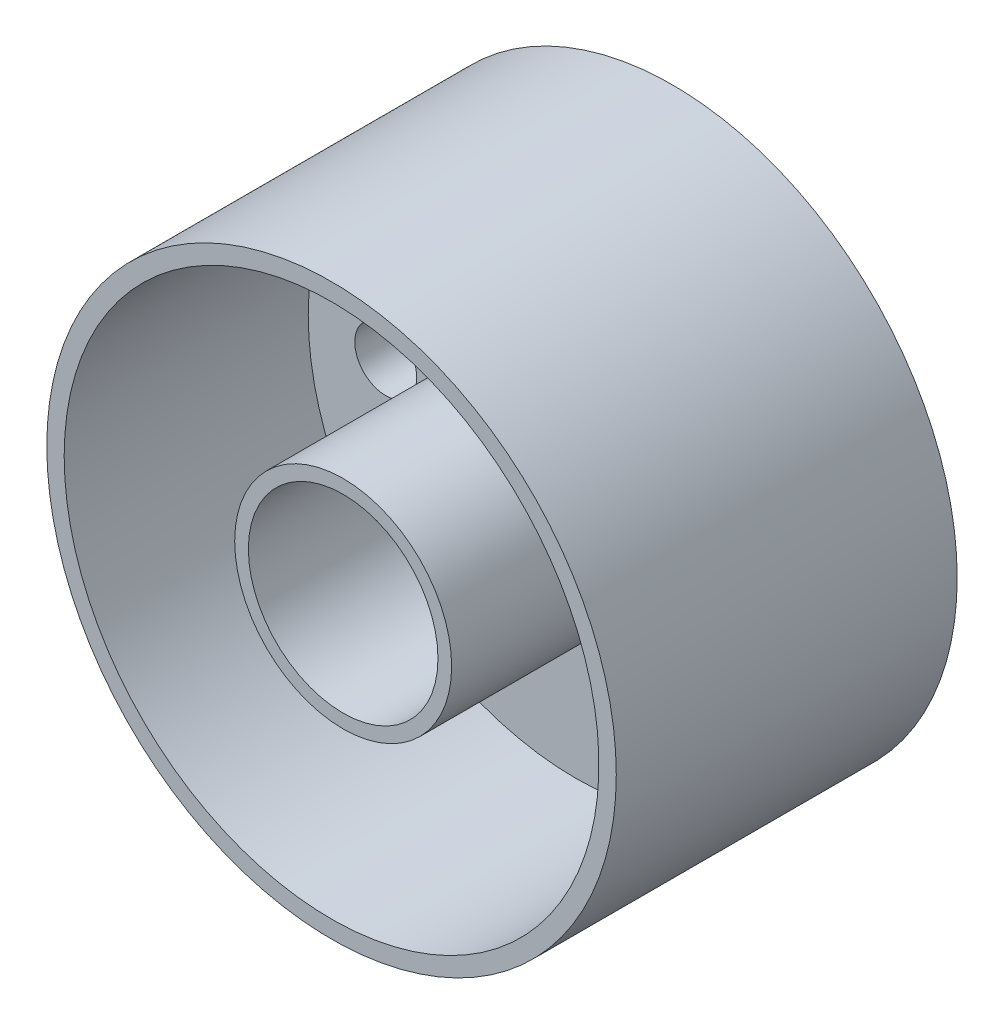
SolidWorks part; units mm, degrees
ref_plane "Front Plane" through (0, 0, 0) normal (0, 0, 1) x (1, 0, 0)
ref_plane "Top Plane" through (0, 0, 0) normal (0, 1, 0) x (1, 0, 0)
ref_plane "Right Plane" through (0, 0, 0) normal (1, 0, 0) x (0, 0, -1)
sketch "Sketch1" plane through (0, 0, 0) normal (0, 0, 1) x (1, 0, 0)
  line L0 (-2.45, 0) -> (-7.35, 0) construction
  circle A0 centre (0, 0) radius 2.45
  circle A1 centre (0, 0) radius 7.35
  circle A2 centre (-4.9, 0) radius 0.8
  circle A3 centre (-2.45, 4.2435) radius 0.8
  circle A4 centre (2.45, 4.2435) radius 0.8
  circle A5 centre (4.9, 0) radius 0.8
  circle A6 centre (2.45, -4.2435) radius 0.8
  circle A7 centre (-2.45, -4.2435) radius 0.8
  point P21 (0, 0)
  dimension "D1" = 4.9
  dimension "D2" = 4.9
  dimension "D3" = 1.6
  dimension "D4" = 6
extrude "Boss-Extrude1" add sketch "Sketch1" along normal blind 1.6
sketch "Sketch2" plane through (0, 0, 1.6) normal (0, 0, 1) x (1, 0, 0)
  circle A0 centre (0, 0) radius 2.8
  circle A1 centre (0, 0) radius 2.4473
extrude "Boss-Extrude3" add sketch "Sketch2" along normal blind 6
sketch "Sketch3" plane through (0, 0, 0) normal (0, 0, -1) x (-1, 0, 0)
  circle A0 centre (0, 0) radius 6.9016
  circle A1 centre (0, 0) radius 7.35
  dimension "D1" = 0.4484
extrude "Boss-Extrude4" add sketch "Sketch3" along normal blind 0.9 and the other way blind 7.9
